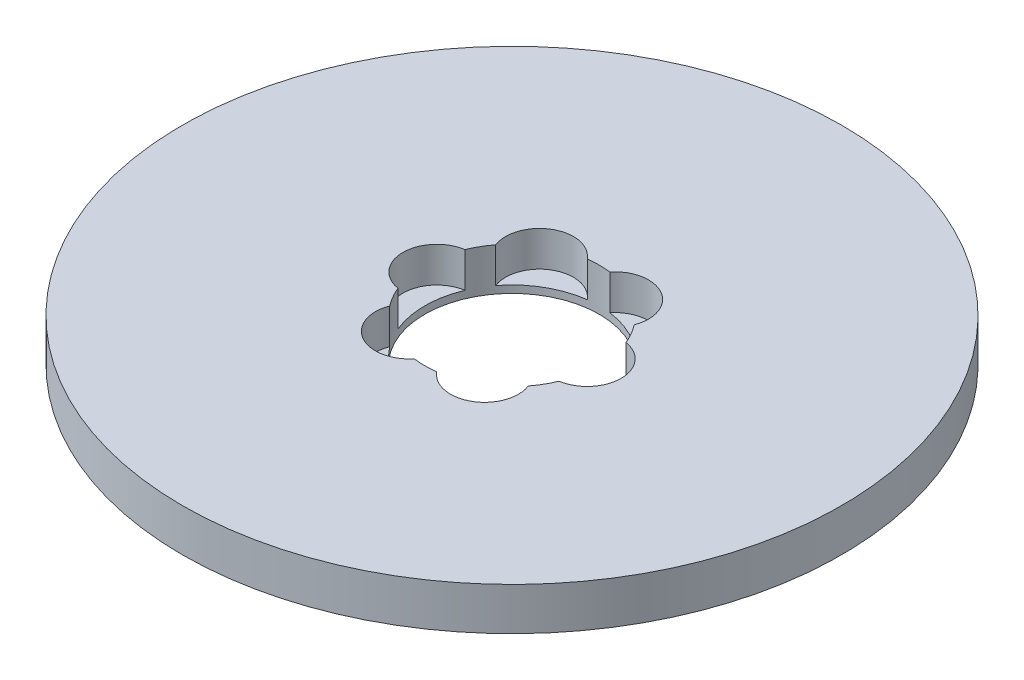
SolidWorks part; units mm, degrees
ref_plane "Front Plane" through (0, 0, 0) normal (0, 0, 1) x (1, 0, 0)
ref_plane "Top Plane" through (0, 0, 0) normal (0, 1, 0) x (1, 0, 0)
ref_plane "Right Plane" through (0, 0, 0) normal (1, 0, 0) x (0, 0, -1)
sketch "Sketch1" plane through (0, 0, 0) normal (0, 1, 0) x (1, 0, 0)
  circle A0 centre (0, 0) radius 85
  dimension "FLANGE_OD" = 170
extrude "Boss-Extrude1" add sketch "Sketch1" along normal blind 11
sketch "Sketch2" plane through (0, 0, 0) normal (0, 1, 0) x (1, 0, 0)
  circle A0 centre (0, 0) radius 22.5
  dimension "BORE_D" = 45
extrude "Cut-Extrude1" cut sketch "Sketch2" along normal through all
sketch "Sketch3" plane through (0, 11, 0) normal (0, 1, 0) x (1, 0, 0)
  circle A0 centre (0, 0) radius 19.387 construction
  circle A1 centre (-19.387, 0) radius 8.7536
  dimension "BOLT_D" = 17.5071
  dimension "BOLT_PCD" = 38.7739
extrude "Cut-Extrude2" cut sketch "Sketch3" against normal blind 9.1052
pattern_circular "CirPattern1" count 6 over 360 about axis through (0, 0, 0) along (0, 1, 0) of "Cut-Extrude2"
